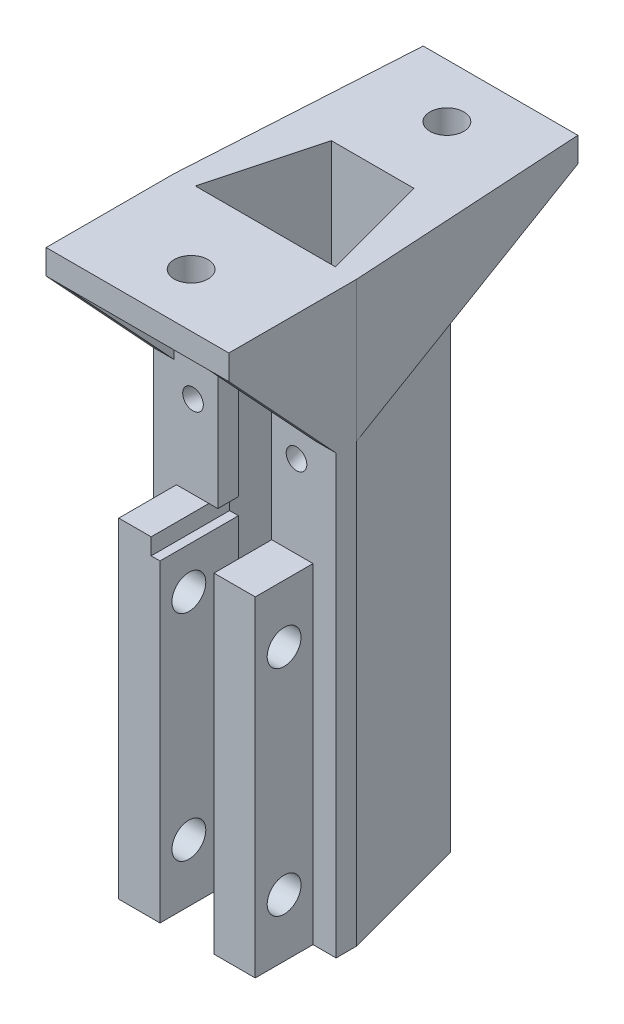
SolidWorks part; units mm, degrees
ref_plane "Front Plane" through (0, 0, 0) normal (0, 0, 1) x (1, 0, 0)
ref_plane "Top Plane" through (0, 0, 0) normal (0, 1, 0) x (1, 0, 0)
ref_plane "Right Plane" through (0, 0, 0) normal (1, 0, 0) x (0, 0, -1)
sketch "Sketch2" plane through (0, 0, 0) normal (0, 1, 0) x (1, 0, 0)
  line L0 (-8.0683, 3.8436) -> (5.7683, 3.8436)
  line L1 (-8.0683, 3.8436) -> (-8.0683, 1.3436)
  line L2 (5.7683, 3.8436) -> (5.7683, 1.3436)
  line L3 (-8.0683, 1.3436) -> (5.7683, 1.3436)
  line L4 (5.7683, 3.8436) -> (9.9215, -11.6564)
  line L5 (5.7683, 3.8436) -> (3.3535, 3.1965)
  line L6 (9.9215, -11.6564) -> (7.5067, -12.3035)
  line L7 (3.3535, 3.1965) -> (7.5067, -12.3035)
  line L8 (-8.0683, 3.8436) -> (-12.2215, -11.6564)
  line L9 (-8.0683, 3.8436) -> (-5.6535, 3.1965)
  line L10 (-12.2215, -11.6564) -> (-9.8067, -12.3035)
  line L11 (-5.6535, 3.1965) -> (-9.8067, -12.3035)
  line L12 (-12.2215, -11.6564) -> (-4.4215, -11.6564)
  line L13 (-12.2215, -11.6564) -> (-12.2215, -14.1564)
  line L14 (-4.4215, -11.6564) -> (-4.4215, -14.1564)
  line L15 (-12.2215, -14.1564) -> (-4.4215, -14.1564)
  line L16 (9.9215, -11.6564) -> (2.1215, -11.6564)
  line L17 (9.9215, -11.6564) -> (9.9215, -14.1564)
  line L18 (2.1215, -11.6564) -> (2.1215, -14.1564)
  line L19 (9.9215, -14.1564) -> (2.1215, -14.1564)
  line L20 (-4.4215, -14.1564) -> (-9.4215, -14.1564)
  line L21 (-4.4215, -14.1564) -> (-4.4215, -21.1564)
  line L22 (-9.4215, -14.1564) -> (-9.4215, -21.1564)
  line L23 (-4.4215, -21.1564) -> (-9.4215, -21.1564)
  line L24 (2.1215, -14.1564) -> (7.1215, -14.1564)
  line L25 (2.1215, -14.1564) -> (2.1215, -21.1564)
  line L26 (7.1215, -14.1564) -> (7.1215, -21.1564)
  line L27 (2.1215, -21.1564) -> (7.1215, -21.1564)
  point P0 (-6.15, 1.3436)
  point P21 (3.85, 1.3436)
  point P24 (7.3334, -11.6564)
  point P25 (-9.6333, -11.6564)
  dimension "D1" = 0
  dimension "D2" = 2.5
  dimension "D3" = 2.5
  dimension "D4" = 2.5
  dimension "D5" = 10
  dimension "D6" = 360
  dimension "D7" = 13
  dimension "D8" = 2.5
  dimension "D9" = 2.5
  dimension "D10" = 13
  dimension "D11" = 5
  dimension "D12" = 5
  dimension "D13" = 105
  dimension "D14" = 7.8
  dimension "D15" = 7.8
  dimension "D16" = 105
  dimension "D17" = 16.9667
  dimension "D18" = 6.5431
  dimension "D19" = 7
  dimension "D20" = 7
extrude "Boss-Extrude1" add sketch "Sketch2" along normal blind 40 contours L16 L4 L2 L3 L7 | L9 L11 L3 L7 L5 L0 | L8 L12 L11 L3 L1 | L5 L7 L3 L2 | L11 L9 L1 L3 | L13 L15 L14 L12 L11 L10 | L12 L10 L11 | L6 L16 L7 | L19 L17 L6 L7 L16 L18 | L25 L27 L26 L19 | L23 L21 L15 L22 region at (-7.0264, 0, -2.4857) region at (-9.164, 0, 4.9784) region at (-1.15, 0, -2.635) region at (6.8641, 0, 4.9784) region at (4.7264, 0, -2.4857) region at (-10.5538, 0, 11.8721) region at (-8.2214, 0, 12.9528) region at (5.9214, 0, 12.9528) region at (8.2539, 0, 11.8721) region at (-6.9215, 0, 17.6564) region at (4.6215, 0, 17.6564)
sketch "Sketch3" plane through (-9.4215, 0, 0) normal (-1, 0, 0) x (0, 0, 1)
  line L0 (21.1564, 40) -> (21.1564, 0) construction
  line L1 (14.1564, 40) -> (14.1564, 0) construction
  line L2 (14.1564, 40) -> (21.1564, 40) construction
  line L3 (14.1564, 0) -> (21.1564, 0) construction
  circle A0 centre (17.6564, 33) radius 2.05
  circle A1 centre (17.6564, 7) radius 2.05
  dimension "D5" = 4.1
  dimension "D6" = 4.1
  dimension "D1" = 3.5
  dimension "D2" = 3.5
  dimension "D3" = 3.5
  dimension "D4" = 3.5
  dimension "D7" = 7
  dimension "D8" = 7
extrude "Cut-Extrude2" cut sketch "Sketch3" against normal blind 40
sketch "Sketch4" plane through (0, 40, 0) normal (0, 1, 0) x (1, 0, 0)
  line L0 (-9.6333, -11.6564) -> (-6.15, 1.3436)
  line L1 (-6.15, 1.3436) -> (3.85, 1.3436)
  line L2 (3.85, 1.3436) -> (7.3334, -11.6564)
  line L3 (7.3334, -11.6564) -> (2.1215, -11.6564)
  line L4 (2.1215, -11.6564) -> (2.1215, -14.1564)
  line L5 (2.1215, -11.6564) -> (2.1215, -21.1564) construction
  line L6 (2.1215, -14.1564) -> (9.9215, -14.1564)
  line L7 (9.9215, -14.1564) -> (9.9215, -11.6564)
  line L8 (9.9215, -11.6564) -> (5.7683, 3.8436)
  line L9 (5.7683, 3.8436) -> (-8.0683, 3.8436)
  line L10 (-8.0683, 3.8436) -> (-12.2215, -11.6564)
  line L11 (-12.2215, -11.6564) -> (-12.2215, -14.1564)
  line L12 (-12.2215, -14.1564) -> (-4.4215, -14.1564)
  line L13 (-4.4215, -11.6564) -> (-4.4215, -21.1564) construction
  line L14 (-4.4215, -14.1564) -> (-4.4215, -11.6564)
  line L33 (-6.15, 1.3436) -> (3.85, 1.3436)
  line L34 (3.85, 1.3436) -> (7.3334, -11.6564)
  line L35 (7.3334, -11.6564) -> (2.1215, -11.6564)
  line L36 (2.1215, -11.6564) -> (2.1215, -21.1564)
  line L37 (2.1215, -21.1564) -> (7.1215, -21.1564)
  line L38 (7.1215, -21.1564) -> (7.1215, -14.1564)
  line L39 (7.1215, -14.1564) -> (9.9215, -14.1564)
  line L40 (9.9215, -14.1564) -> (9.9215, -11.6564)
  line L41 (9.9215, -11.6564) -> (5.7683, 3.8436)
  line L42 (5.7683, 3.8436) -> (-8.0683, 3.8436)
  line L43 (-8.0683, 3.8436) -> (-12.2215, -11.6564)
  line L44 (-12.2215, -11.6564) -> (-12.2215, -14.1564)
  line L45 (-12.2215, -14.1564) -> (-9.4215, -14.1564)
  line L46 (-9.4215, -14.1564) -> (-9.4215, -21.1564)
  line L47 (-9.4215, -21.1564) -> (-4.4215, -21.1564)
  line L48 (-4.4215, -21.1564) -> (-4.4215, -11.6564)
  line L49 (-4.4215, -11.6564) -> (-9.6333, -11.6564)
  line L50 (-9.6333, -11.6564) -> (-6.15, 1.3436)
  line L51 (-6.15, 1.3436) -> (3.85, 1.3436)
  line L52 (3.85, 1.3436) -> (7.3334, -11.6564)
  line L53 (7.3334, -11.6564) -> (2.1215, -11.6564)
  line L54 (2.1215, -11.6564) -> (2.1215, -21.1564)
  line L55 (2.1215, -21.1564) -> (7.1215, -21.1564)
  line L56 (7.1215, -21.1564) -> (7.1215, -14.1564)
  line L57 (7.1215, -14.1564) -> (9.9215, -14.1564)
  line L58 (9.9215, -14.1564) -> (9.9215, -11.6564)
  line L59 (9.9215, -11.6564) -> (5.7683, 3.8436)
  line L60 (5.7683, 3.8436) -> (-8.0683, 3.8436)
  line L61 (-8.0683, 3.8436) -> (-12.2215, -11.6564)
  line L62 (-12.2215, -11.6564) -> (-12.2215, -14.1564)
  line L63 (-12.2215, -14.1564) -> (-9.4215, -14.1564)
  line L64 (-9.4215, -14.1564) -> (-9.4215, -21.1564)
  line L65 (-9.4215, -21.1564) -> (-4.4215, -21.1564)
  line L66 (-4.4215, -21.1564) -> (-4.4215, -11.6564)
  line L68 (-9.6333, -11.6564) -> (-6.15, 1.3436)
  line M19 (-6.15, 1.3436) -> (3.85, 1.3436)
  line M20 (3.85, 1.3436) -> (7.3334, -11.6564)
  line M21 (7.3334, -11.6564) -> (2.1215, -11.6564)
  line M22 (2.1215, -11.6564) -> (2.1215, -21.1564)
  line M25 (7.1215, -14.1564) -> (9.9215, -14.1564)
  line M26 (9.9215, -14.1564) -> (9.9215, -11.6564)
  line M27 (9.9215, -11.6564) -> (5.7683, 3.8436)
  line M28 (5.7683, 3.8436) -> (-8.0683, 3.8436)
  line M29 (-8.0683, 3.8436) -> (-12.2215, -11.6564)
  line M30 (-12.2215, -11.6564) -> (-12.2215, -14.1564)
  line M31 (-12.2215, -14.1564) -> (-9.4215, -14.1564)
  line M34 (-4.4215, -21.1564) -> (-4.4215, -11.6564)
  line M35 (-4.4215, -11.6564) -> (-9.6333, -11.6564)
  line M36 (-9.6333, -11.6564) -> (-6.15, 1.3436)
  dimension "D1" = 0
extrude "Boss-Extrude2" add sketch "Sketch4" along normal blind 30 contours L12 L6 M31 M34 M35 M36 M19 M20 M21 M22 M25 M26 M27 M28 M29 M30 region at (-7.0274, 40, 11.9418)
sketch "Sketch7" plane through (0, 0, -3.8436) normal (0, 0, -1) x (-1, 0, 0)
  line L0 (-5.7683, 70) -> (-5.7683, 0) construction
  line L1 (5.4917, 38) -> (0.9917, 38)
  line L2 (5.4917, 38) -> (5.4917, 40)
  line L3 (5.4917, 40) -> (0.9917, 40)
  line L4 (0.9917, 38) -> (0.9917, 40)
  line L5 (8.0683, 70) -> (8.0683, 0) construction
  line L6 (8.0683, 0) -> (-5.7683, 0) construction
  point P4 (0.9917, 39)
  dimension "D1" = 6.76
  dimension "D2" = 4.5
  dimension "D3" = 2
  dimension "D4" = 2.5766
  dimension "D5" = 38
extrude "Cut-Extrude3" cut sketch "Sketch7" against normal through all
sketch "Sketch10" plane through (0, 0, -3.8436) normal (0, 0, -1) x (-1, 0, 0)
  line L0 (5.4917, 40) -> (0.9917, 40)
  line L1 (5.4917, 40) -> (5.4917, 115)
  line L2 (0.9917, 40) -> (0.9917, 115)
  line L3 (5.4917, 115) -> (0.9917, 115)
  dimension "D1" = 75
extrude "Cut-Extrude5" cut sketch "Sketch10" against normal blind 1.5
sketch "Sketch13" plane through (0, 0, -2.3436) normal (0, 0, -1) x (-1, 0, 0)
  line L1 (5.4917, 40) -> (8.2917, 40)
  line L2 (5.4917, 40) -> (5.4917, 42)
  line L3 (5.4917, 42) -> (8.2917, 42)
  line L4 (8.2917, 40) -> (8.2917, 42)
  dimension "D1" = 2
  dimension "D2" = 2.8
extrude "Cut-Extrude7" cut sketch "Sketch13" along normal blind 1.5
sketch "Sketch15" plane through (0, 0, -3.8436) normal (0, 0, -1) x (-1, 0, 0)
  line L0 (8.0683, 42) -> (5.4917, 42) construction
  line L1 (8.0683, 40) -> (6.5683, 40)
  line L2 (8.0683, 40) -> (8.0683, 42)
  line L3 (8.0683, 42) -> (6.5683, 42)
  line L4 (6.5683, 40) -> (6.5683, 42)
  dimension "D1" = 1.5
extrude "Cut-Extrude8" cut sketch "Sketch15" along direction (-0.2588, 0, 0.9659) on the side against the normal blind 18.5
sketch "Sketch16" plane through (0, 0, 14.1564) normal (0, 0, 1) x (1, 0, 0)
  line L0 (-4.4215, 70) -> (-4.4215, 40) construction
  line L1 (-12.2215, 70) -> (-4.4215, 70) construction
  circle A0 centre (-7.4215, 50) radius 1.25
  dimension "D1" = 20
  dimension "D2" = 2.5
  dimension "D4" = 3
extrude "Cut-Extrude9" cut sketch "Sketch16" along direction (-0.2588, 0, 0.9659) on the side against the normal blind 3.5
sketch "Sketch17" plane through (0, 0, 14.1564) normal (0, 0, 1) x (1, 0, 0)
  line L0 (2.1215, 70) -> (2.1215, 40) construction
  line L1 (2.1215, 70) -> (9.9215, 70) construction
  circle A0 centre (5.1215, 50) radius 1.25
  dimension "D1" = 2.5
  dimension "D2" = 3
  dimension "D3" = 20
extrude "Cut-Extrude10" cut sketch "Sketch17" along direction (0.2588, 0, 0.9659) on the side against the normal blind 3.5
sketch "Sketch18" plane through (0, 0, 11.6564) normal (0, 0, -1) x (-1, 0, 0)
  line L0 (-9.9215, 70) -> (-9.9215, 0) construction
  line L1 (-9.9215, 70) -> (12.2215, 70)
  line L2 (-9.9215, 70) -> (-9.9215, 67)
  line L3 (-9.9215, 67) -> (12.2215, 67)
  line L4 (12.2215, 70) -> (12.2215, 67)
  line L5 (12.2215, 70) -> (12.2215, 42) construction
  dimension "D1" = 3
  dimension "D2" = 0
extrude "Boss-Extrude4" add sketch "Sketch18" against normal blind 15.5
sketch "Sketch19" plane through (0, 0, -3.8436) normal (0, 0, -1) x (-1, 0, 0)
  line L0 (-5.7683, 70) -> (-5.7683, 0) construction
  line L1 (8.0683, 70) -> (-5.7683, 70)
  line L2 (8.0683, 70) -> (8.0683, 67)
  line L3 (8.0683, 67) -> (-5.7683, 67)
  line L4 (-5.7683, 70) -> (-5.7683, 67)
  dimension "D1" = 3
extrude "Boss-Extrude5" add sketch "Sketch19" along normal blind 13 and the other way blind 2 contours L1 L4 L3 L2
sketch "Sketch21" plane through (-12.2215, 0, 0) normal (-1, 0, 0) x (0, 0, 1)
  line L0 (27.1564, 67) -> (14.1564, 53)
  line L1 (14.1564, 67) -> (14.1564, 0) construction
  line L2 (14.1564, 53) -> (14.1564, 67)
  line L3 (14.1564, 67) -> (27.1564, 67)
  dimension "D1" = 14
extrude "Boss-Extrude6" add sketch "Sketch21" against normal blind 2.5
sketch "Sketch22" plane through (9.9215, 0, 0) normal (1, 0, 0) x (0, 0, -1)
  line L0 (-27.1564, 67) -> (-14.1564, 67)
  line L1 (-14.1564, 67) -> (-14.1564, 53)
  line L2 (-14.1564, 67) -> (-14.1564, 0) construction
  line L3 (-14.1564, 53) -> (-27.1564, 67)
  dimension "D1" = 14
extrude "Boss-Extrude8" add sketch "Sketch22" against normal blind 2.5
sketch "Sketch23" plane through (9.9215, 0, 0) normal (1, 0, 0) x (0, 0, -1)
  line L0 (-11.6564, 70) -> (-11.6564, 53)
  line L1 (-11.6564, 70) -> (-11.6564, 0) construction
  line L2 (16.8436, 70) -> (16.8436, 67)
  line L3 (16.8436, 70) -> (-11.6564, 70)
  line L4 (16.8436, 67) -> (-11.6564, 53)
  dimension "D1" = 28.5
  dimension "D2" = 28.5
  dimension "D3" = 17
  dimension "D4" = 3
extrude "Boss-Extrude9" add sketch "Sketch23" against normal blind 4.2
sketch "Sketch24" plane through (-12.2215, 0, 0) normal (-1, 0, 0) x (0, 0, 1)
  line L0 (11.6564, 70) -> (-16.8436, 70)
  line L1 (-16.8436, 70) -> (-16.8436, 67)
  line L2 (-16.8436, 67) -> (11.6564, 53)
  line L3 (11.6564, 70) -> (11.6564, 42) construction
  line L4 (11.6564, 53) -> (11.6564, 70)
  dimension "D1" = 17
  dimension "D2" = 28.5
  dimension "D3" = 3
extrude "Boss-Extrude10" add sketch "Sketch24" against normal blind 4.2
sketch "Sketch25" plane through (0, 70, 0) normal (0, 1, 0) x (1, 0, 0)
  line L2 (-6.15, 1.3436) -> (3.85, 1.3436) construction
  line L3 (5.7215, -11.6564) -> (-8.0215, -11.6564) construction
  circle A0 centre (-1.15, 10.3436) radius 2.05
  circle A1 centre (-1.15, -20.6564) radius 2.05
  dimension "D1" = 4.1
  dimension "D2" = 4.1
  dimension "D3" = 9
  dimension "D4" = 9
  dimension "D5" = 6.8715
  dimension "D6" = 6.8715
  dimension "D7" = 5
  dimension "D8" = 5
extrude "Cut-Extrude12" cut sketch "Sketch25" against normal blind 3.5
sketch "Sketch26" plane through (0, 47.3099, 23.2399) normal (0, -0.8976, -0.4409) x (-1, 0, 0)
  line L0 (-5.7215, 12.9056) -> (-7.3334, 12.9056)
  line L1 (-7.3334, 12.9056) -> (-5.7215, 19.6076)
  line L2 (-5.7215, 19.6076) -> (-5.7215, 12.9056)
  line L3 (8.0215, 12.9056) -> (8.0215, 19.6076)
  line L4 (8.0215, 19.6076) -> (9.6333, 12.9056)
  line L5 (9.6333, 12.9056) -> (8.0215, 12.9056)
extrude "Cut-Extrude13" cut sketch "Sketch26" along direction (0, -1, 0) on the side against the normal through all
sketch "Sketch27" plane through (0, 47.3099, 23.2399) normal (0, -0.8976, -0.4409) x (-1, 0, 0)
  line L0 (12.2215, 12.9056) -> (10.5215, 44.6586)
  line L1 (12.2215, 44.6586) -> (8.0215, 44.6586) construction
  line L2 (10.5215, 44.6586) -> (12.2215, 44.6586)
  line L3 (12.2215, 44.6586) -> (12.2215, 12.9056)
  line L4 (-9.9215, 12.9056) -> (-9.9215, 44.6586)
  line L5 (-9.9215, 44.6586) -> (-8.2215, 44.6586)
  line L6 (-5.7215, 44.6586) -> (-9.9215, 44.6586) construction
  line L7 (-8.2215, 44.6586) -> (-9.9215, 12.9056)
  dimension "D1" = 2.5
  dimension "D2" = 2.5
extrude "Cut-Extrude14" cut sketch "Sketch27" along direction (0, -1, 0) on the side against the normal through all
